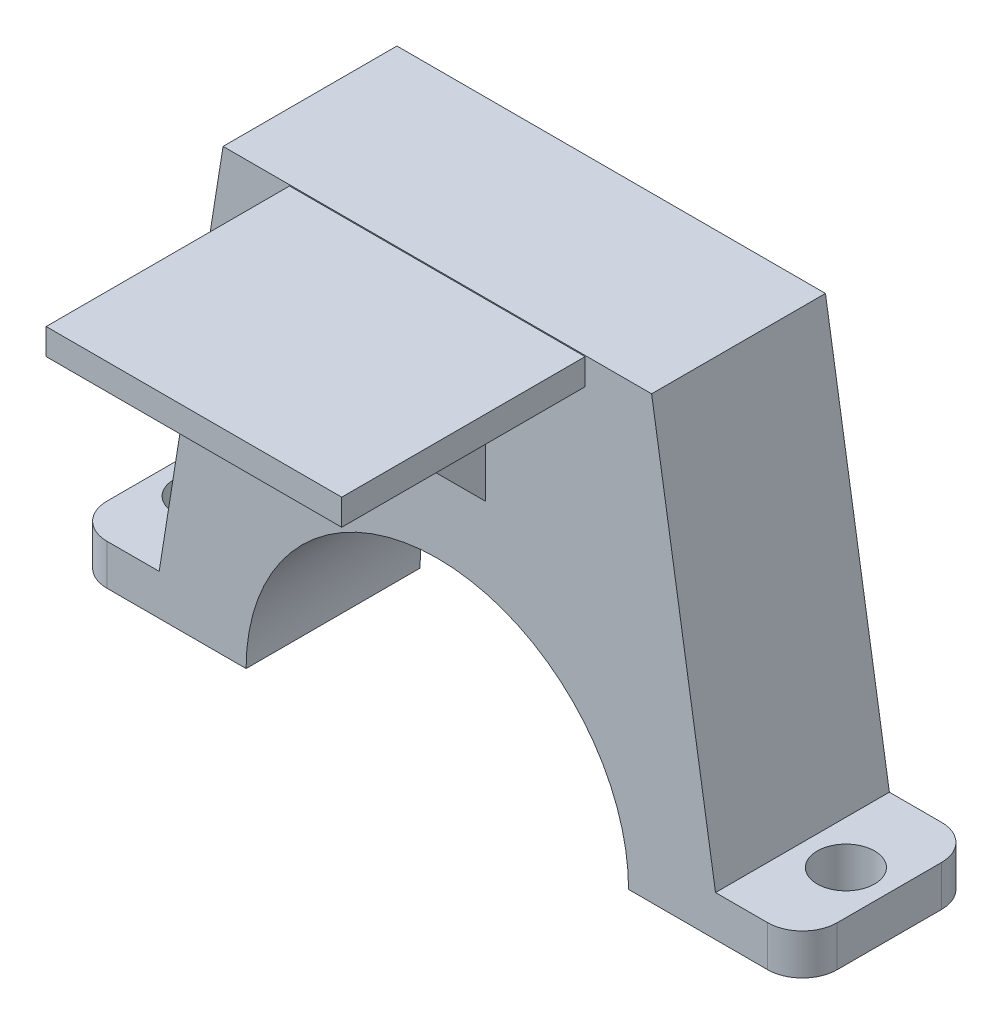
SolidWorks part; units mm, degrees
ref_plane "Plan de face" through (0, 0, 0) normal (0, 0, 1) x (1, 0, 0)
ref_plane "Plan de dessus" through (0, 0, 0) normal (0, 1, 0) x (1, 0, 0)
ref_plane "Plan de droite" through (0, 0, 0) normal (1, 0, 0) x (0, 0, -1)
sketch "Sketch1" plane through (0, 0, 0) normal (0, 0, 1) x (1, 0, 0)
  line L0 (-21, 0) -> (-11, 0)
  line L5 (0, 0) -> (-11, 0) construction
  line L11 (-16, 2.3437) -> (-21, 2.3437)
  line L12 (-21, 0) -> (-21, 2.3437)
  line L13 (0, 0) -> (0, 11) construction
  line L14 (-16, 0) -> (-16, 2.3437) construction
  line L15 (0, 11) -> (0, 16.1707)
  line L17 (-12.3245, 25.3503) -> (0, 25.3503)
  line L18 (0, 25.3503) -> (0, 16.1707)
  line L19 (-12.3245, 25.3503) -> (-16, 2.3437)
  arc A2 (-11, 0) -> (0, 11) centre (0, 0) cw
  point P0 (0, 0)
  dimension "D1" = 11
  dimension "D2" = 10
  dimension "D3" = 11
  dimension "D4" = 5
extrude "Boss-Extrude1" add sketch "Sketch1" along normal blind 10
sketch "Sketch2" plane through (0, 2.3437, 0) normal (0, 1, 0) x (1, 0, 0)
  line L0 (-21, 0) -> (-16, -10) construction
  circle A0 centre (-18.5, -5) radius 1.65
  dimension "D1" = 3.3
extrude "External_holes" cut sketch "Sketch2" against normal blind 10
fillet "Fillet1" radius 2 2 edges at (-21, 1.1719, 0) (-21, 1.1719, 10)
mirror "Mirror1" of "External_holes", "Fillet1", "Boss-Extrude1"
sketch "Sketch4" plane through (0, 0, 10) normal (0, 0, 1) x (1, 0, 0)
  line L1 (-8.5, 25.2897) -> (8.5, 25.2897)
  line L2 (-8.5, 25.2897) -> (-8.5, 23.7897)
  line L3 (-8.5, 23.7897) -> (8.5, 23.7897)
  line L4 (8.5, 25.2897) -> (8.5, 23.7897)
  line L5 (-8.5, 25.2897) -> (8.5, 23.7897) construction
  line L6 (-8.5, 23.7897) -> (8.5, 25.2897) construction
  point P0 (0, 24.5397)
  point P5 (0, 24.4527)
  dimension "D1" = 17
  dimension "D2" = 1.5
extrude "Boss-Extrude2" add sketch "Sketch4" along normal blind 14 contours L3 L4 L1 L2
sketch "Sketch5" plane through (0, 23.7897, 0) normal (0, -1, 0) x (1, 0, 0)
  line L0 (11, 10) -> (-11, 10) construction
  line L1 (-2.7609, 18.5713) -> (2.7609, 18.5713)
  line L2 (-2.7609, 18.5713) -> (-2.7609, 10)
  line L3 (-2.7609, 10) -> (2.7609, 10)
  line L4 (2.7609, 18.5713) -> (2.7609, 10)
  line L5 (-2.7609, 18.5713) -> (2.7609, 10) construction
  line L6 (-2.7609, 10) -> (2.7609, 18.5713) construction
  point P0 (0, 14.2856)
extrude "Boss-Extrude3" add sketch "Sketch5" along normal blind 10
chamfer "Chamfer1" distance 10 angle 45 1 edges at (0, 13.7897, 18.5713)
